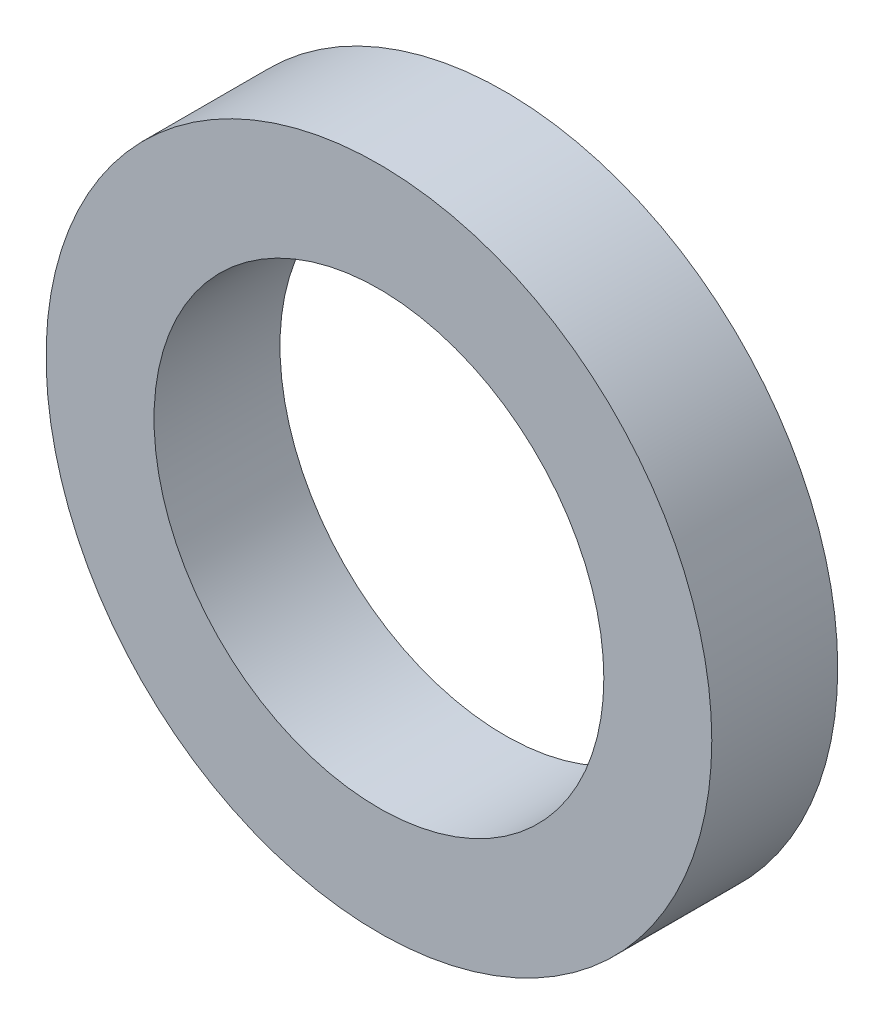
SolidWorks part; units mm, degrees
ref_plane "Спереди" through (0, 0, 0) normal (0, 0, 1) x (1, 0, 0)
ref_plane "Сверху" through (0, 0, 0) normal (0, 1, 0) x (1, 0, 0)
ref_plane "Справа" through (0, 0, 0) normal (1, 0, 0) x (0, 0, -1)
sketch "Эскиз1" plane through (0, 0, 0) normal (0, 0, 1) x (1, 0, 0)
  circle A0 centre (0, 0) radius 18.5
  circle A2 centre (0, 0) radius 12.5
  circle A4 centre (0, 0) radius 17
  circle A5 centre (0, 0) radius 14
  dimension "D1" = 1.5
  dimension "D2" = 1.5
extrude "Бобышка-Вытянуть2" add sketch "Эскиз1" along normal blind 3.5 and the other way blind 3.5 contours A0 A4 | A5 A2 region at (-17.9767, 0, 0) region at (-13.604, 0, 0)
extrude "Бобышка-Вытянуть3" add sketch "Эскиз1<4>" along normal blind 3.5 and the other way blind 3.5 contours A4 A5 region at (-16.5192, 0, 0)
sketch "Эскиз1<4>" plane through (0, 0, 0) normal (0, 0, 1) x (1, 0, 0) same geometry as "Эскиз1"
